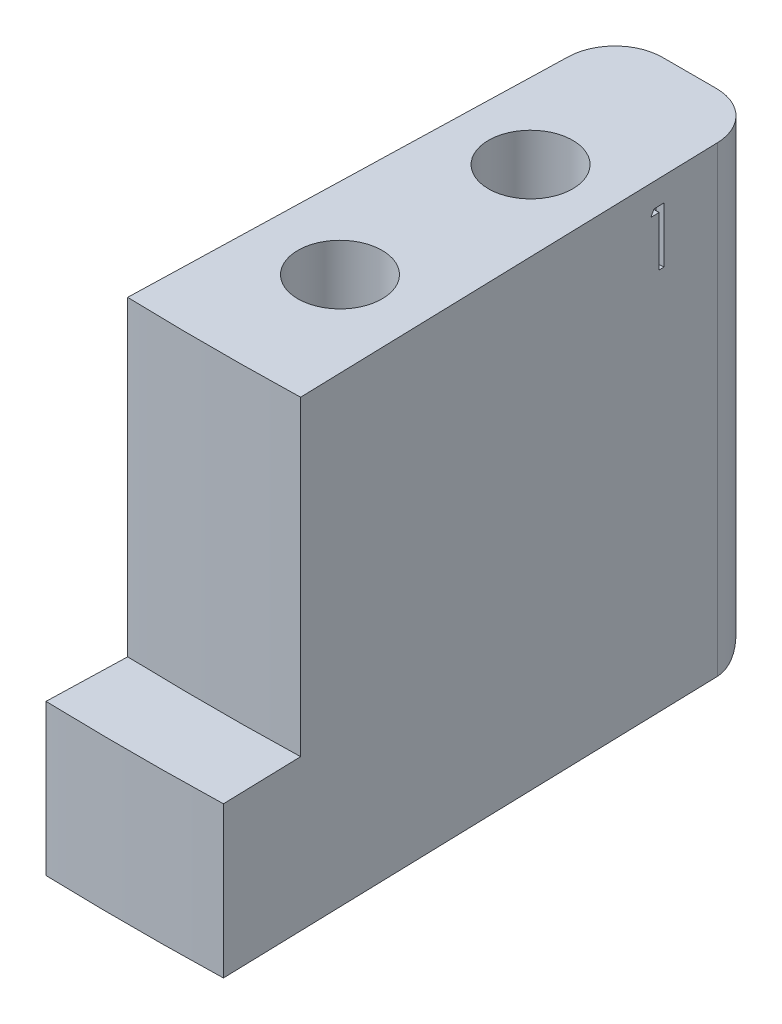
SolidWorks part; units mm, degrees
ref_plane "前视基准面" through (0, 0, 0) normal (0, 0, 1) x (1, 0, 0)
ref_plane "上视基准面" through (0, 0, 0) normal (0, 1, 0) x (1, 0, 0)
ref_plane "右视基准面" through (0, 0, 0) normal (1, 0, 0) x (0, 0, -1)
ref_axis "顶盖中心轴" through (0, -55, 0) along (0, 1, 0)
sketch "草图1" plane through (0, 0, 0) normal (0, 1, 0) x (1, 0, 0)
  line L0 (-4.7487, -170.0072) -> (-4.8586, -173.9402) construction
  line L1 (0, 0) -> (0, -125.794) construction
  line L3 (-4.6089, -165) -> (4.6089, -165)
  line L4 (-4.6089, -165) -> (-5.5843, -199.922)
  line L5 (4.6089, -165) -> (5.5843, -199.922)
  arc A0 (-5.4447, -194.924) -> (5.4447, -194.924) centre (0, 0) ccw
  arc A1 (-5.5843, -199.922) -> (5.5843, -199.922) centre (0, 0) ccw
  dimension "D1" = 1.6
  dimension "D2" = 195
  dimension "D4" = 200
  dimension "D3" = 165
extrude "主体" add sketch "草图1" along normal blind 29.1 contours L4 A0 L5 L3 region at (0, 0, 180.4033)
extrude "插销" add sketch "草图1<3>" along normal blind 9.5 contours L4 A1 L5 A0 region at (0, 0, 197.4849)
sketch "草图1<3>" plane through (0, 0, 0) normal (0, 1, 0) x (1, 0, 0) same geometry as "草图1"
ref_plane "对称面" through (0, 0, 0) normal (1, 0, 0) x (0, 0, -1)
fillet "圆角1" radius 3 3 edges at (-4.6089, 14.55, 165) (4.6089, 14.55, 165) (0, 0, 165)
hole_wizard "M5 间隙孔1" positions "草图4" profile "草图5" hole size "M5" standard "ISO" end condition up to next
sketch "草图4" plane through (0, 29.1, 0) normal (0, 1, 0) x (1, 0, 0)
  line L0 (0, -13.75) -> (0, 13.75) construction
  point P0 (0, -187)
  point P2 (0, -175)
  dimension "D1" = 175
  dimension "D2" = 187
sketch "草图5" plane through (0, 29.1, 187) normal (1, 0, 0) x (0, 0, 1)
  line L0 (0, 0) -> (0, 29.1)
  line L1 (0, 29.1) -> (2.65, 29.1)
  line L2 (2.65, 29.1) -> (2.65, 0)
  line L5 (2.65, 0) -> (0, 0)
  line L11 (0, -6.35) -> (0, 107.95) construction
  dimension "通孔孔直径" = 5.3
  dimension "通孔孔深度" = 29.1
sketch "草图6" plane through (0, 0, 0) normal (0, -1, 0) x (1, 0, 0)
  line L1 (0, 179.6188) -> (-4, 177.3094)
  line L2 (-4, 177.3094) -> (-4, 172.6906)
  line L3 (-4, 172.6906) -> (0, 170.3812)
  line L4 (0, 170.3812) -> (4, 172.6906)
  line L5 (4, 172.6906) -> (4, 177.3094)
  line L6 (4, 177.3094) -> (0, 179.6188)
  line L7 (0, 191.6188) -> (-4, 189.3094)
  line L8 (-4, 189.3094) -> (-4, 184.6906)
  line L9 (-4, 184.6906) -> (0, 182.3812)
  line L10 (0, 182.3812) -> (4, 184.6906)
  line L11 (4, 184.6906) -> (4, 189.3094)
  line L12 (4, 189.3094) -> (0, 191.6188)
  circle A0 centre (0, 175) radius 4 construction
  circle A1 centre (0, 187) radius 4 construction
  dimension "D1" = 8
  dimension "D2" = 8
extrude "切除-拉伸1" cut sketch "草图6" against normal blind 5
sketch "草图7" plane through (0, 0, 0) normal (0.9996, 0, -0.0279) x (-0.0279, 0, -0.9996)
  line L0 (-167.9817, 0.0012) -> (-167.9817, 29.1) construction
  line L1 (-167.9817, 29.1) -> (-195, 29.1) construction
  text T0 "1"
  dimension "D1" = 5
  dimension "D2" = 5
extrude "切除-拉伸2" cut sketch "草图7" against normal blind 0.5
